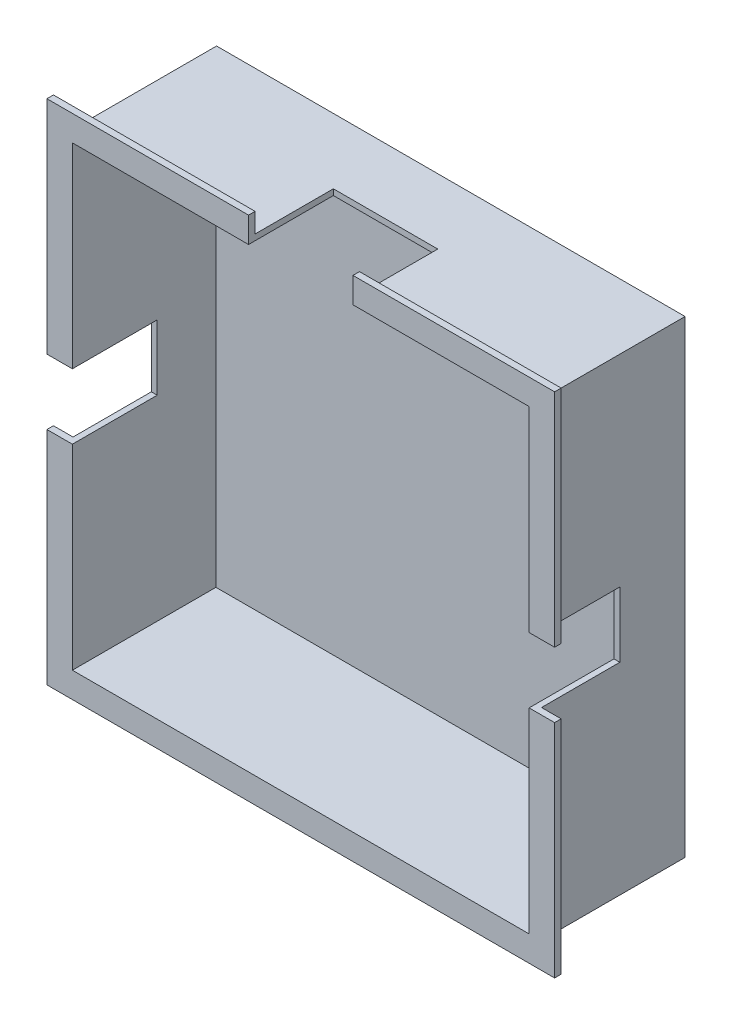
SolidWorks part; units mm, degrees
ref_plane "Front Plane" through (0, 0, 0) normal (0, 0, 1) x (1, 0, 0)
ref_plane "Top Plane" through (0, 0, 0) normal (0, 1, 0) x (1, 0, 0)
ref_plane "Right Plane" through (0, 0, 0) normal (1, 0, 0) x (0, 0, -1)
sketch "Sketch1" plane through (0, 0, 0) normal (0, 0, 1) x (1, 0, 0)
  line L0 (0, 0) -> (0, 70)
  line L1 (0, 0) -> (70, 0)
  line L2 (70, 0) -> (70, 70)
  line L3 (70, 70) -> (0, 70)
  line L4 (0, 70) -> (-0.9, 70)
  line L5 (-0.9, 70) -> (-0.9, 0)
  line L6 (-0.9, 0) -> (0, 0)
  line L7 (-0.9, 0) -> (-0.9, -0.9)
  line L8 (-0.9, -0.9) -> (70.9, -0.9)
  line L9 (70.9, -0.9) -> (70.9, 70.9)
  line L10 (70.9, 70.9) -> (-0.9, 70.9)
  line L11 (-0.9, 70.9) -> (-0.9, 70)
  line L12 (-0.2661, 40) -> (0, 40)
  line L13 (0, 40) -> (-0.9, 40)
  line L14 (0, 30) -> (-0.9, 30)
  line L15 (70, 40) -> (70.9, 40)
  line L16 (70.9, 40) -> (70.9, 30)
  line L17 (70.9, 30) -> (70, 30)
  line L18 (35, 70) -> (35, 70.9)
  line L19 (27, 70) -> (27, 70.9)
  line L20 (43, 70) -> (43, 70.9)
  line L21 (-0.9, 30) -> (-3.9, 30)
  line L22 (-3.9, 30) -> (-3.9, -3.9)
  line L23 (-3.9, -3.9) -> (73.9, -3.9)
  line L24 (73.9, -3.9) -> (73.9, 73.9)
  line L25 (73.9, 73.9) -> (-3.9, 73.9)
  line L26 (-3.9, 73.9) -> (-3.9, 30)
  line L27 (-0.9, 40) -> (-3.9, 40)
  line L28 (70.9, 30) -> (73.9, 30)
  line L29 (70.9, 40) -> (73.9, 40)
  line L30 (35, 70.9) -> (35, 73.9)
  line L31 (43, 70.9) -> (43, 73.9)
  point P3 (35, 70)
  point P6 (35, 0)
  point P7 (0, 35)
  point P8 (70, 35)
  point P9 (35, 35)
  point P10 (0, 40)
  point P11 (0, 30)
  point P12 (70, 40)
  point P13 (70, 30)
  point P27 (27, 70)
  point P34 (43, 70)
  dimension "D1" = 70
  dimension "D2" = 70
  dimension "D3" = 5
  dimension "D4" = 5
  dimension "D5" = 5
  dimension "D6" = 5
  dimension "D7" = 0.9
  dimension "D8" = 71.8
  dimension "D9" = 71.8
  dimension "D10" = 0.9
  dimension "D11" = 35
  dimension "D12" = 35
  dimension "D13" = 0.9
  dimension "D14" = 0.2661
  dimension "D15" = 8
  dimension "D16" = 8
  dimension "D17" = 0.9
  dimension "D18" = 8
  dimension "D19" = 3
  dimension "D20" = 3
  dimension "D21" = 3
  dimension "D22" = 3
  dimension "D23" = 3
  dimension "D24" = 8
extrude "Boss-Extrude2" add sketch "Sketch1" along normal blind 23 contours L13 L12 L0 L4 L5 | L20 L3 L2 L15 L9 L10 | L3 L19 L10 L11 L4 | L9 L17 L2 L1 L6 L7 L8 | L0 L14 L5 L6 region at (-0.45, 15, 0) region at (35, -0.7817, 0) region at (-0.45, 55, 0) region at (13.05, 70.45, 0) region at (70.4163, 55, 0)
sketch "Sketch2" plane through (0, 0, 0) normal (0, 1, 0) x (1, 0, 0)
  line L0 (0, 0) -> (0, -1)
  line L1 (0, -23) -> (0, 0) construction
  line L2 (0, -1) -> (70, -1)
  line L3 (70, -23) -> (70, 0) construction
  line L4 (70, -1) -> (70, 0)
  line L5 (70, 0) -> (0, 0)
  dimension "D1" = 1
extrude "Boss-Extrude3" add sketch "Sketch2" along normal blind 70
extrude "Boss-Extrude4" add sketch "Sketch1<5>" along normal blind 10 contours L14 L0 L12 L13 L5 | L3 L20 L10 L18 | L19 L3 L18 L10 | L17 L9 L15 L2 region at (-0.45, 35, 0) region at (70.45, 35, 0) region at (31, 70.45, 0) region at (39, 70.45, 0)
sketch "Sketch1<5>" plane through (0, 0, 0) normal (0, 0, 1) x (1, 0, 0) same geometry as "Sketch1"
sketch "Sketch4" plane through (0, 0, 23) normal (0, 0, 1) x (1, 0, 0)
  line L0 (70.9, 70.9) -> (43, 70.9) construction
  line L1 (-3.9, 73.9043) -> (73.9043, 73.9043)
  line L2 (-3.9, 73.9043) -> (-3.9, -3.9)
  line L3 (-3.9, -3.9) -> (73.9043, -3.9)
  line L4 (73.9043, 73.9043) -> (73.9043, -3.9)
  line L5 (-0.9, 70.9) -> (-0.9, 40) construction
  line L6 (-0.9, -0.9) -> (70.9, -0.9) construction
  line L7 (27, 70.9) -> (27, 73.9043)
  line L8 (43, 70.9) -> (43, 73.9043)
  line L9 (-0.9, 40) -> (-3.9, 40)
  line L10 (-0.9, 30) -> (-3.9, 30)
  line L11 (70.9, 30) -> (73.9043, 30)
  line L12 (70.9, 40) -> (73.9043, 40)
  line L13 (-0.9, 40) -> (-0.9, 70.9)
  line L14 (-0.9, 70.9) -> (70.9, 70.9)
  line L15 (70.9, 70.9) -> (70.9, 40)
  line L16 (70.9, 30) -> (70.9, -0.9)
  line L17 (70.9, -0.9) -> (-0.9, -0.9)
  line L18 (-0.9, -0.9) -> (-0.9, 30)
  line M9 (27, 70.9) -> (-0.9, 70.9)
  line M10 (-0.9, 70.9) -> (-0.9, 40)
  dimension "D1" = 3.0043
  dimension "D2" = 3
  dimension "D3" = 3
extrude "Boss-Extrude5" add sketch "Sketch4" against normal blind 1 contours L9 L7 L1 L2 M10 M9 | L17 L18 L10 L2 L3 L4 L11 L16 | L14 L15 L12 L4 L1 L8 region at (11.55, 73.4456, 23) region at (58.4521, 73.4455, 23) region at (-2.4, 29.1513, 23)
